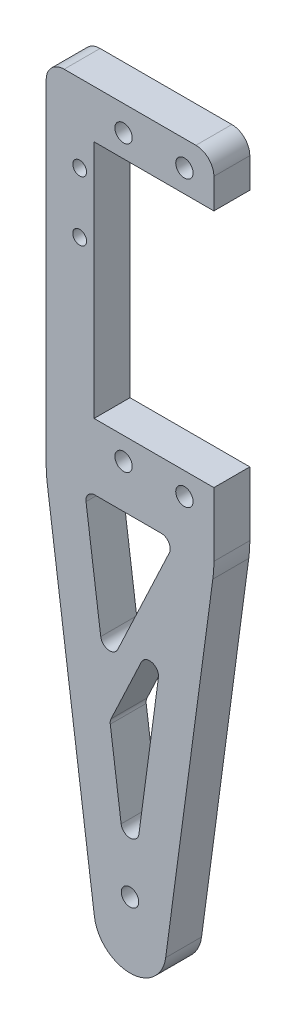
SolidWorks part; units mm, degrees
material "ABS"
ref_plane "Front" through (0, 0, 0) normal (0, 0, 1) x (1, 0, 0)
ref_plane "Top" through (0, 0, 0) normal (0, 1, 0) x (1, 0, 0)
ref_plane "Right" through (0, 0, 0) normal (1, 0, 0) x (0, 0, -1)
sketch "Esquisse1" plane through (0, 0, 0) normal (0, 0, 1) x (1, 0, 0)
  line L0 (-14, -30) -> (-5.9467, -90)
  line L1 (-14, 30) -> (14, 30)
  line L2 (-14, 30) -> (-14, -30)
  line L4 (14, 30) -> (14, 22)
  line L5 (14, -18) -> (14, -30)
  line L6 (14, 22) -> (-6, 22)
  line L8 (5.9467, -90) -> (14, -30)
  line L10 (14, -18) -> (-6, -18)
  line L11 (-6, 22) -> (-6, -18)
  arc A0 (-5.9467, -90) -> (5.9467, -90) centre (0, -89.2018) ccw
  point P0 (0, 0)
  point P14 (-14, 0)
  point P21 (0, 30)
  dimension "D2" = 6
  dimension "D1" = 60
  dimension "D3" = 28
  dimension "D5" = 20
  dimension "D6" = 40
  dimension "D7" = 8
  dimension "D8" = 60
extrude "Boss.-Extru.1" add sketch "Esquisse1" along normal blind 6
fillet "Congé1" radius 3 2 edges at (-14, 30, 3) (14, 30, 3)
fillet "Congé2" radius 20 2 edges at (14, -30, 3) (-14, -30, 3)
sketch "Esquisse2" plane through (0, 0, 6) normal (0, 0, 1) x (1, 0, 0)
  line L0 (14, -18) -> (-6, -18) construction
  circle A1 centre (9.08, -21.75) radius 1.45
  circle A2 centre (-1.08, -21.75) radius 1.45
  circle A3 centre (-1.08, 25.75) radius 1.45
  circle A4 centre (9.08, 25.75) radius 1.45
  point P4 (4, -18)
  dimension "D1" = 5.08
  dimension "D2" = 3.75
  dimension "D3" = 2.9
  dimension "D5" = 2
  dimension "D4" = 2
extrude "Enlèv. mat.-Extru.1" cut sketch "Esquisse2" against normal up to next
sketch "Esquisse3" plane through (0, 0, 6) normal (0, 0, 1) x (1, 0, 0)
  line L6 (-7.5759, -29) -> (-4.2168, -54.0263)
  line L7 (-4.2168, -54.0263) -> (7.5759, -29)
  line L8 (7.5759, -29) -> (-7.5759, -29)
  line L15 (6.0349, -40.4813) -> (-3.3591, -60.4169)
  line L16 (-4.2168, -54.0263) -> (-0.8118, -79.3949) construction
  line L17 (-3.3591, -60.4169) -> (0, -85.4433)
  line L18 (0, -85.4433) -> (6.0349, -40.4813)
  line L22 (14, -18) -> (-6, -18) construction
  line L23 (5.9467, -90) -> (13.8222, -31.3244) construction
  line L24 (-13.8222, -31.3244) -> (-5.9467, -90) construction
  line L25 (7.5759, -29) -> (6.0349, -40.4813) construction
  point P7 (-0.8118, -85.4433)
  point P9 (-4.4312, -58.5109)
  point P11 (-0.8118, -85.4433)
  dimension "D1" = 6.5
  dimension "D2" = 6.5
  dimension "D3" = 3.5
  dimension "D4" = 11
extrude "Enlèv. mat.-Extru.2" cut sketch "Esquisse3" against normal up to next
fillet "Congé3" radius 1.5 6 edges at (7.5759, -29, 3) (-4.2168, -54.0263, 3) (-7.5759, -29, 3) (0, -85.4433, 3) (-3.3591, -60.4169, 3) (6.0349, -40.4813, 3)
sketch "Esquisse4" plane through (0, 0, 6) normal (0, 0, 1) x (1, 0, 0)
  circle A0 centre (0, -84.2018) radius 1.45
  arc A2 (-5.9467, -90) -> (5.9467, -90) centre (0, -89.2018) ccw construction
  point P2 (0, -84.1748)
  point P3 (0, 0)
  point P4 (0, 0)
  point P5 (0, -82.6985)
  point P6 (0, 0)
  point P7 (0, 0)
  point P11 (0, -95.2018)
  dimension "D1" = 2.9
  dimension "D2" = 11
extrude "Enlèv. mat.-Extru.3" cut sketch "Esquisse4" against normal blind 6
sketch "Esquisse5" plane through (0, 0, 6) normal (0, 0, 1) x (1, 0, 0)
  line L0 (-6, 22) -> (14, 22) construction
  line L1 (-6, -18) -> (-6, 22) construction
  circle A0 centre (-8.41, 17) radius 1.15
  circle A1 centre (-8.41, 7) radius 1.15
  dimension "D1" = 2.3
  dimension "D2" = 5
  dimension "D3" = 2.41
  dimension "D4" = 2
extrude "Enlèv. mat.-Extru.4" cut sketch "Esquisse5" against normal blind 6
